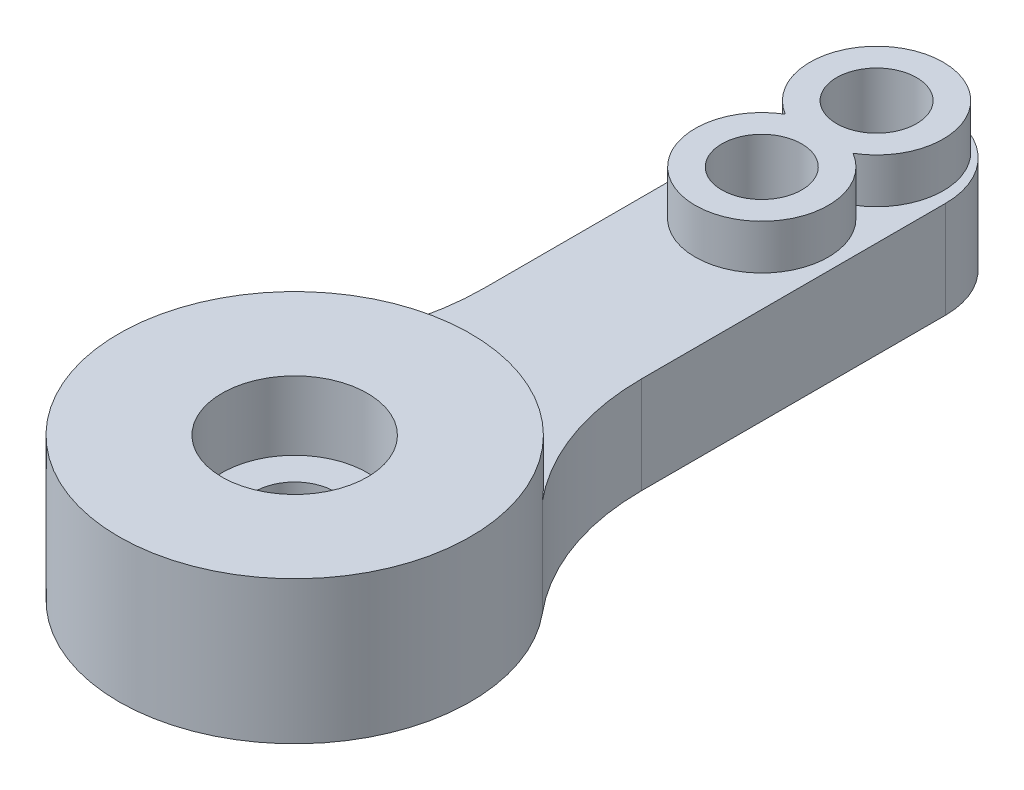
SolidWorks part; units mm, degrees
material "Alliage 1060"
ref_plane "Plan de face" through (0, 0, 0) normal (0, 0, 1) x (1, 0, 0)
ref_plane "Plan de dessus" through (0, 0, 0) normal (0, 1, 0) x (1, 0, 0)
ref_plane "Plan de droite" through (0, 0, 0) normal (1, 0, 0) x (0, 0, -1)
sketch "Esquisse1" plane through (0, 0, 0) normal (0, 1, 0) x (1, 0, 0)
  line L0 (-3.245, 6.4944) -> (-3.245, 23.625)
  line L2 (3.245, 23.625) -> (3.245, 6.4944)
  arc A0 (-3.245, 6.4944) -> (3.245, 6.4944) centre (0, 0) ccw
  arc A2 (3.245, 23.625) -> (-3.245, 23.625) centre (0, 23.625) ccw
  dimension "D2" = 14.52
  dimension "D3" = 6.49
  dimension "D1" = 6.49
  dimension "D4" = 23.625
extrude "Boss.-Extru.1" add sketch "Esquisse1" along normal blind 4
sketch "Esquisse3" plane through (0, 4, 0) normal (0, 1, 0) x (1, 0, 0)
  circle A0 centre (0, 0) radius 7.26
  dimension "D1" = 14.52
extrude "Boss.-Extru.2" add sketch "Esquisse3" along normal blind 1.9
sketch "Esquisse2" plane through (0, 4, 0) normal (0, 1, 0) x (1, 0, 0)
  circle A0 centre (0, 0) radius 1.65
  circle A1 centre (0, 19.28) radius 1.65
  circle A3 centre (0, 24.02) radius 1.65
  dimension "D1" = 3.3
  dimension "D2" = 19.28
  dimension "D3" = 24.02
extrude "Enlèv. mat.-Extru.1" cut sketch "Esquisse2" against normal through all and the other way through all
sketch "Esquisse4" plane through (0, 4, 0) normal (0, 1, 0) x (1, 0, 0)
  arc A0 (1.3948, 21.65) -> (-1.3948, 21.65) centre (0, 24.02) ccw
  arc A1 (-1.3948, 21.65) -> (1.3948, 21.65) centre (0, 19.28) ccw
  circle A2 centre (0, 24.02) radius 1.65
  circle A3 centre (0, 19.28) radius 1.65
  dimension "D1" = 5.5
  dimension "D2" = 3.3
extrude "Boss.-Extru.3" add sketch "Esquisse4" along normal blind 1.85
fillet "Congé1" radius 10 2 edges at (-3.245, 2, -6.4944) (3.245, 2, -6.4944)
sketch "Esquisse5" plane through (0, 5.9, 0) normal (0, 1, 0) x (1, 0, 0)
  circle A0 centre (0, 0) radius 3
  dimension "D1" = 6
extrude "Enlèv. mat.-Extru.2" cut sketch "Esquisse5" against normal blind 2.84
